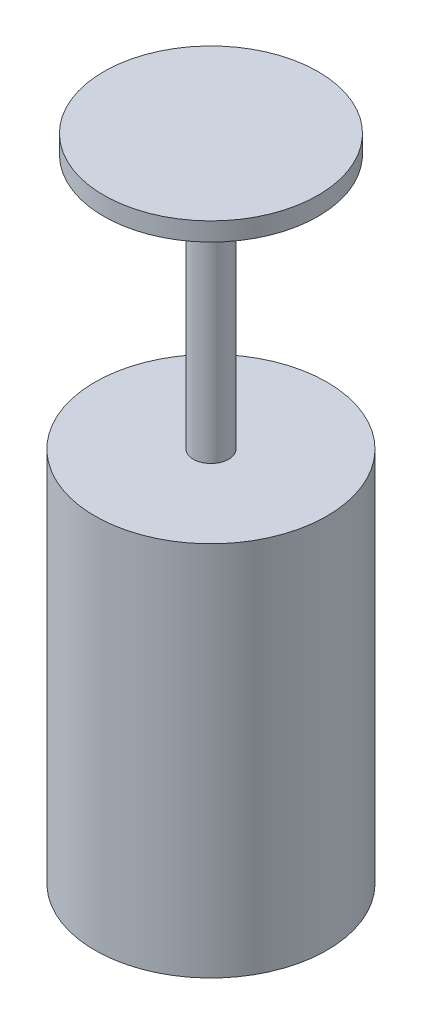
SolidWorks part; units mm, degrees
ref_plane "Front Plane" through (0, 0, 0) normal (0, 0, 1) x (1, 0, 0)
ref_plane "Top Plane" through (0, 0, 0) normal (0, 1, 0) x (1, 0, 0)
ref_plane "Right Plane" through (0, 0, 0) normal (1, 0, 0) x (0, 0, -1)
sketch "Sketch1" plane through (0, 0, 0) normal (0, 0, 1) x (1, 0, 0)
  line L1 (0, 0) -> (16.0655, 0)
  line L2 (0, 0) -> (0, -52.07)
  line L3 (0, -52.07) -> (16.0655, -52.07)
  line L4 (16.0655, 0) -> (16.0655, -52.07)
  line L5 (0, 0) -> (2.4506, 0)
  line L6 (0, 0) -> (0, 35.306)
  line L7 (0, 35.306) -> (2.4506, 35.306)
  line L8 (2.4506, 0) -> (2.4506, 35.306)
  line L9 (0, 35.306) -> (14.8364, 35.306)
  line L10 (0, 35.306) -> (0, 37.846)
  line L11 (0, 37.846) -> (14.8364, 37.846)
  line L12 (14.8364, 35.306) -> (14.8364, 37.846)
  dimension "D1" = 16.0655
  dimension "D2" = 52.07
  dimension "D3" = 89.916
  dimension "D4" = 2.54
revolve "Revolve1" add sketch "Sketch1" angle 360 about L6 region at (1.2253, 17.653, 0) region at (8.0328, -26.035, 0) region at (7.4182, 36.576, 0)
